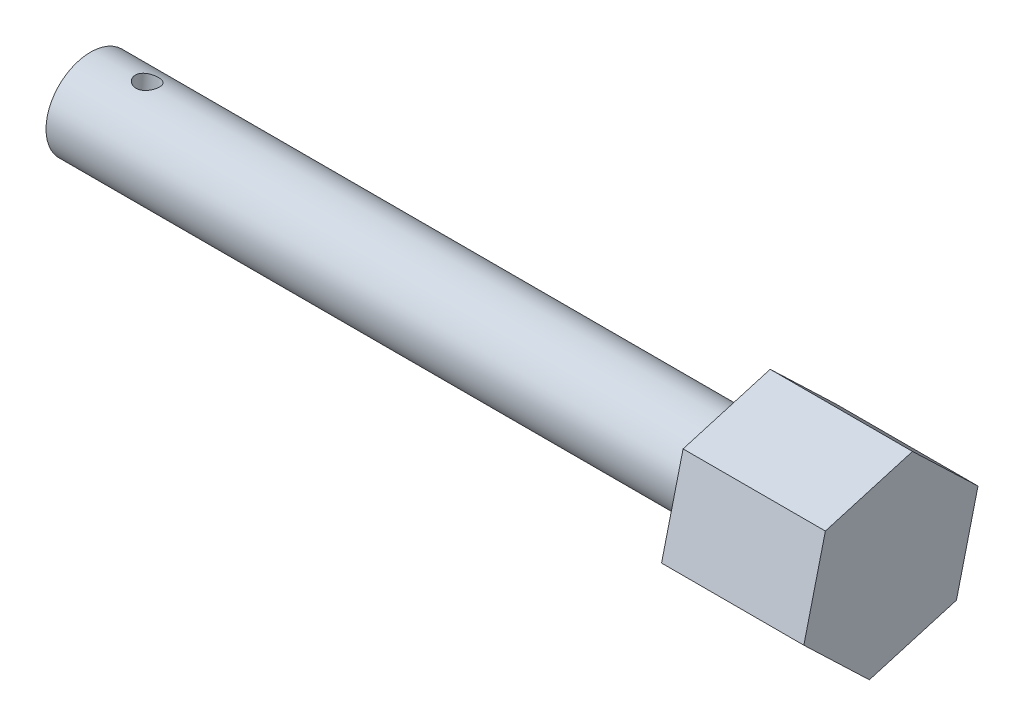
SolidWorks part; units mm, degrees
ref_plane "Front Plane" through (0, 0, 0) normal (0, 0, 1) x (1, 0, 0)
ref_plane "Top Plane" through (0, 0, 0) normal (0, 1, 0) x (1, 0, 0)
ref_plane "Right Plane" through (0, 0, 0) normal (1, 0, 0) x (0, 0, -1)
sketch "Sketch1" plane through (0, 0, 0) normal (1, 0, 0) x (0, 0, -1)
  circle A0 centre (0, 0) radius 3.175
extrude "Boss-Extrude2" add sketch "Sketch1" along normal blind 46.99 contours A0
sketch "Sketch2" plane through (46.99, 0, 0) normal (1, 0, 0) x (0, 0, -1)
  line L1 (-4.6788, 4.4782) -> (-6.2176, -1.8129)
  line L2 (-6.2176, -1.8129) -> (-1.5388, -6.2911)
  line L3 (-1.5388, -6.2911) -> (4.6788, -4.4782)
  line L4 (4.6788, -4.4782) -> (6.2176, 1.8129)
  line L5 (6.2176, 1.8129) -> (1.5388, 6.2911)
  line L6 (1.5388, 6.2911) -> (-4.6788, 4.4782)
  circle A0 centre (0, 0) radius 5.6088 construction
extrude "Boss-Extrude3" add sketch "Sketch2" along normal blind 10.16
sketch "Sketch3" plane through (0, 0, 0) normal (-1, 0, 0) x (0, 0, 1)
  circle A0 centre (0, 0) radius 1.778
  circle A1 centre (0, 0) radius 3.175
extrude "Cut-Extrude1" cut sketch "Sketch3" against normal blind 19.05
sketch "Sketch6" plane through (0, 0, 0) normal (-1, 0, 0) x (0, 0, 1)
  circle A0 centre (0, 0) radius 3.175
extrude "Boss-Extrude5" add sketch "Sketch6" against normal blind 49.022
sketch "Sketch7" plane through (0, 0, 0) normal (-1, 0, 0) x (0, 0, 1)
  line L1 (-0.4893, 0.7146) -> (-0.8635, -0.0664)
  line L2 (-0.8635, -0.0664) -> (-0.3742, -0.781)
  line L3 (-0.3742, -0.781) -> (0.4893, -0.7146)
  line L4 (0.4893, -0.7146) -> (0.8635, 0.0664)
  line L5 (0.8635, 0.0664) -> (0.3742, 0.781)
  line L6 (0.3742, 0.781) -> (-0.4893, 0.7146)
  circle A0 centre (0, 0) radius 0.75 construction
extrude "Cut-Extrude5" cut sketch "Sketch7" against normal blind 38.1
sketch "Sketch8" plane through (0, 0.7478, -0.0575) normal (0, -0.9971, 0.0767) x (1, 0, 0)
  line L0 (46.99, 3.175) -> (0, 3.175) construction
  line L1 (0, 3.175) -> (0, -3.175) construction
  circle A0 centre (3.81, 0) radius 0.8001
  dimension "D1" = 1.6002
  dimension "D2" = 3.175
  dimension "D3" = 3.81
extrude "Cut-Extrude6" cut sketch "Sketch8" against normal blind 2.54
cosmetic thread "Cosmetic Thread1" parameters "D2"=2.1844
cosmetic thread "Cosmetic Thread2" parameters "D2"=2.1844
